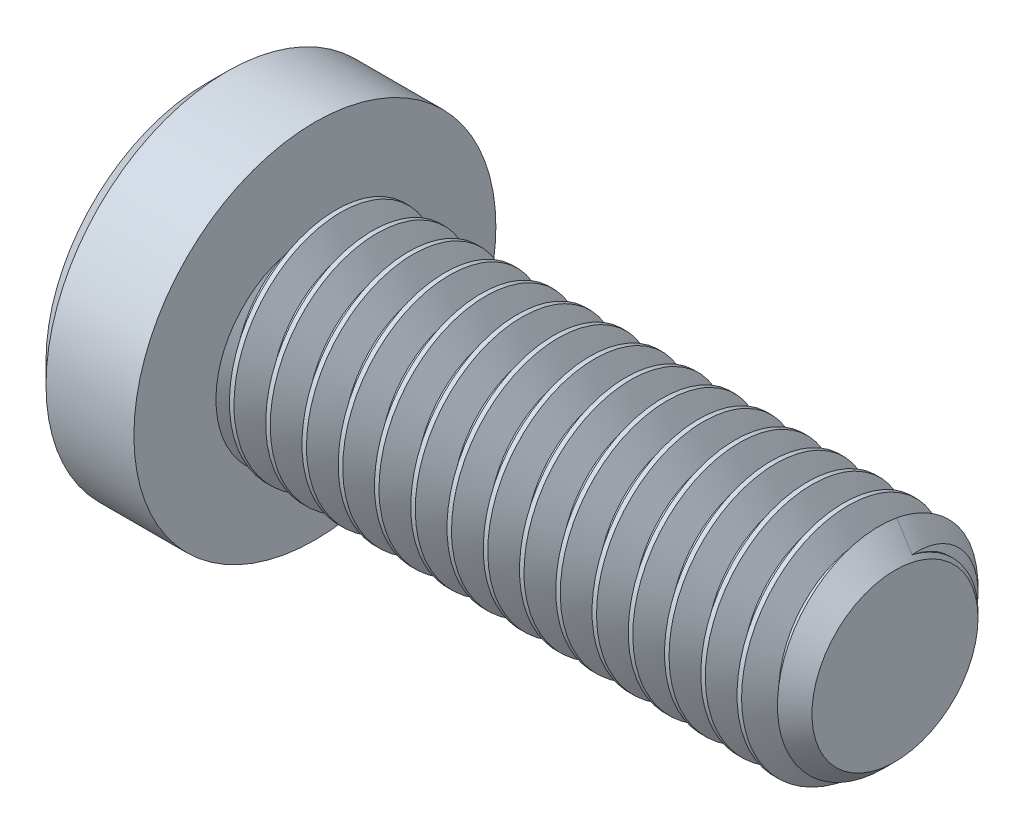
SolidWorks part; units mm, degrees
ref_plane "Front Plane" through (0, 0, 0) normal (0, 0, 1) x (1, 0, 0)
ref_plane "Top Plane" through (0, 0, 0) normal (0, 1, 0) x (1, 0, 0)
ref_plane "Right Plane" through (0, 0, 0) normal (1, 0, 0) x (0, 0, -1)
sketch "Sketch1" plane through (0, 0, 0) normal (0, 0, 1) x (1, 0, 0)
  line L0 (6.35, 0) -> (-6.35, 0) construction
  line L1 (6.35, 2.413) -> (6.35, -2.413) construction
  line L2 (-6.35, 3.9624) -> (-6.35, -3.9624) construction
  line L3 (-6.35, 3.9624) -> (-8.274, 3.9624) construction
  line L4 (-8.274, 3.9624) -> (-8.7312, 3.5052) construction
  line L5 (-8.7312, 3.5052) -> (-8.7312, -3.5052) construction
  line L6 (-8.7312, -3.5052) -> (-8.274, -3.9624) construction
  line L7 (-8.274, -3.9624) -> (-6.35, -3.9624) construction
  point P7 (-6.9024, 0)
  point P12 (3.175, -2.413)
  dimension "D1" = 45
  dimension "D2" = 3.175
  dimension "Dec." = 4.826
  dimension "Length" = 12.7
  dimension "Head Dia" = 7.9248
  dimension "Head Height" = 2.3813
  dimension "Hex Depth" = 1.8288
  dimension "Chamfer" = 0.4572
ref_plane "Plane1" through (6.35, 0, 0) normal (1, 0, 0) x (0, 0, -1)
ref_plane "Plane2" through (-8.7312, 0, 0) normal (1, 0, 0) x (0, 0, -1)
sketch "Sketch2" plane through (6.35, 0, 0) normal (1, 0, 0) x (0, 0, -1)
  circle A0 centre (0, 0) radius 2.413
extrude "Boss-Extrude1" add sketch "Sketch2" against normal up to vertex (12.7 mm away) up to point (-6.35, 0, 0)
sketch "Sketch3" plane through (6.35, 0, 0) normal (1, 0, 0) x (0, 0, -1)
  circle A0 centre (0, 0) radius 2.413 construction
  circle A1 centre (0, 0) radius 2.413
curve "Helix/Spiral1" pitch 0.7937 height 13.4937 radius 2.413 centre (6.35, 0, 0) axis (-1, 0, 0) start towards (0, 1, 0) parameters "Pitch"=0.7937
chamfer "Chamfer1" distance 0.5953 angle 45 1 edges at (6.35, 0, -2.413)
sketch "Sketch5" plane through (0, 0, 0) normal (0, 0, 1) x (1, 0, 0)
  line L0 (6.0027, 2.413) -> (6.6973, 2.413)
  line L1 (6.6973, 2.413) -> (6.3996, 1.8974)
  line L2 (6.3996, 1.8974) -> (6.3004, 1.8974)
  line L3 (6.3004, 1.8974) -> (6.0027, 2.413)
  line L4 (6.35, 1.8974) -> (6.35, 2.413) construction
  line L5 (6.1516, 2.1552) -> (6.5484, 2.1552) construction
  dimension "D1" = 60
  dimension "D2" = 0.3969
  dimension "D3" = 0.0992
sweep "Cut-Sweep1" cut profiles "Sketch5" path "Helix/Spiral1"
sketch "Sketch4" plane through (-8.7312, 0, 0) normal (1, 0, 0) x (0, 0, -1)
  line L0 (-3.9624, 0.7937) -> (3.9624, 0.7937) construction
  line L1 (0, 1.3748) -> (-1.1906, 0.6874)
  line L2 (-1.1906, 0.6874) -> (-1.1906, -0.6874)
  line L3 (-1.1906, -0.6874) -> (0, -1.3748)
  line L4 (0, -1.3748) -> (1.1906, -0.6874)
  line L5 (1.1906, -0.6874) -> (1.1906, 0.6874)
  line L6 (1.1906, 0.6874) -> (0, 1.3748)
  line L7 (0, 0) -> (0, 0.7937) construction
  circle A0 centre (0, 0) radius 1.1906 construction
  dimension "D1" = 7.9248
  dimension "Hex Size" = 2.3813
  dimension "D2" = 0.7937
sketch "Sketch6" plane through (0, 0, 0) normal (0, 0, 1) x (1, 0, 0)
  line L0 (-8.274, 3.9624) -> (-8.7312, 3.5052) construction
  line L1 (-6.35, 3.9624) -> (-8.274, 3.9624) construction
  line L2 (-6.35, 3.9624) -> (-6.35, -3.9624) construction
  line L3 (-8.7312, 3.5052) -> (-8.7312, -3.5052) construction
  line L4 (-8.274, 3.9624) -> (-8.7312, 3.5052)
  line L5 (-6.35, 3.9624) -> (-8.274, 3.9624)
  line L6 (-6.35, 3.9624) -> (-6.35, 0)
  line L7 (-8.7312, 3.5052) -> (-8.7312, 0)
  line L8 (-6.35, 0) -> (-8.7312, 0) construction
  line L9 (-6.35, 0) -> (-8.7312, 0)
revolve "Revolve1" add sketch "Sketch6" angle 360 about L8
extrude "Cut-Extrude1" cut sketch "Sketch4" along normal up to vertex (1.8288 mm away) up to point (-6.9024, 0, 0)
sketch "Sketch8" plane through (-8.7312, 0, 0) normal (-1, 0, 0) x (0, 0, 1)
  circle A1 centre (0, 0) radius 1.3748
extrude "Cut-Extrude2" cut sketch "Sketch8" against normal through all draft 45
equation "\"D3@Helix/Spiral1\" = \"Length@Sketch1\"+\"Pitch@Helix/Spiral1\""
equation "\"D3@Sketch5\" = \"Pitch@Helix/Spiral1\"*.125"
equation "\"D2@Sketch5\" = \"Pitch@Helix/Spiral1\"*.50"
equation "\"D1@Chamfer1\" = \"Pitch@Helix/Spiral1\"*.75"
equation "\"D2@Sketch1\" = \"Pitch@Helix/Spiral1\"*4"
equation "\"D1@Sketch4\" = \"Head Dia@Sketch1\""
